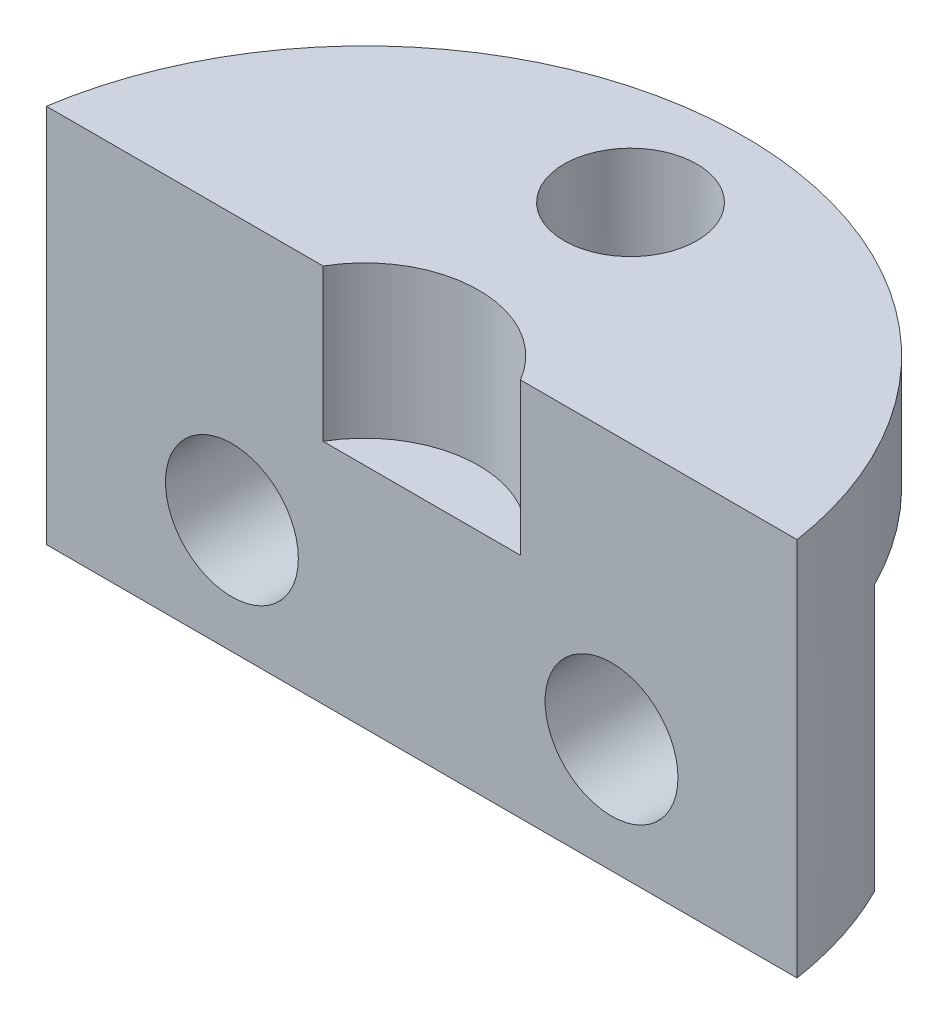
SolidWorks part; units mm, degrees
material "ABS"
ref_plane "Спереди" through (0, 0, 0) normal (0, 0, 1) x (1, 0, 0)
ref_plane "Сверху" through (0, 0, 0) normal (0, 1, 0) x (1, 0, 0)
ref_plane "Справа" through (0, 0, 0) normal (1, 0, 0) x (0, 0, -1)
sketch "Эскиз1" plane through (0, 0, 0) normal (0, 1, 0) x (1, 0, 0)
  circle A0 centre (0, 0) radius 10
  dimension "D1" = 20
extrude "Бобышка-Вытянуть1" add sketch "Эскиз1" along normal blind 10
sketch "Эскиз2" plane through (0, 0, 0) normal (0, 1, 0) x (1, 0, 0)
  line L1 (-12.3821, 1.5) -> (14.971, 1.5)
  line L2 (-12.3821, 1.5) -> (-12.3821, -10.2937)
  line L3 (-12.3821, -10.2937) -> (14.971, -10.2937)
  line L4 (14.971, 1.5) -> (14.971, -10.2937)
  dimension "D1" = 1.5
extrude "Вырез-Вытянуть1" cut sketch "Эскиз2" against normal blind 10 and the other way blind 10
sketch "Эскиз3" plane through (0, 10, 0) normal (0, 1, 0) x (1, 0, 0)
  circle A0 centre (0, 7) radius 1.75
  dimension "D2" = 3.5
  dimension "D1" = 7
extrude "Вырез-Вытянуть2" cut sketch "Эскиз3" against normal through all
sketch "Эскиз4" plane through (0, 10, 0) normal (0, 1, 0) x (1, 0, 0)
  circle A0 centre (0, 0) radius 3
  dimension "D1" = 6
extrude "Вырез-Вытянуть3" cut sketch "Эскиз4" against normal blind 4
sketch "Эскиз5" plane through (0, 0, 0) normal (0, -1, 0) x (1, 0, 0)
  line L1 (-11.0045, -4.5) -> (12.2564, -4.5)
  line L2 (-11.0045, -4.5) -> (-11.0045, -11.5)
  line L3 (-11.0045, -11.5) -> (12.2564, -11.5)
  line L4 (12.2564, -4.5) -> (12.2564, -11.5)
  dimension "D1" = 4.5
  dimension "D2" = 7
extrude "Вырез-Вытянуть5" cut sketch "Эскиз5" against normal blind 7
sketch "Эскиз6" plane through (0, 0, -1.5) normal (0, 0, 1) x (1, 0, 0)
  line L0 (0, 0) -> (0, 2.8608) construction
  line L1 (-2.5981, 10) -> (-9.8869, 10) construction
  circle A0 centre (-5, 3) radius 1.75
  circle A1 centre (5, 3) radius 1.75
  dimension "D1" = 3.5
  dimension "D2" = 10
  dimension "D3" = 7
extrude "Вырез-Вытянуть6" cut sketch "Эскиз6" against normal blind 7
